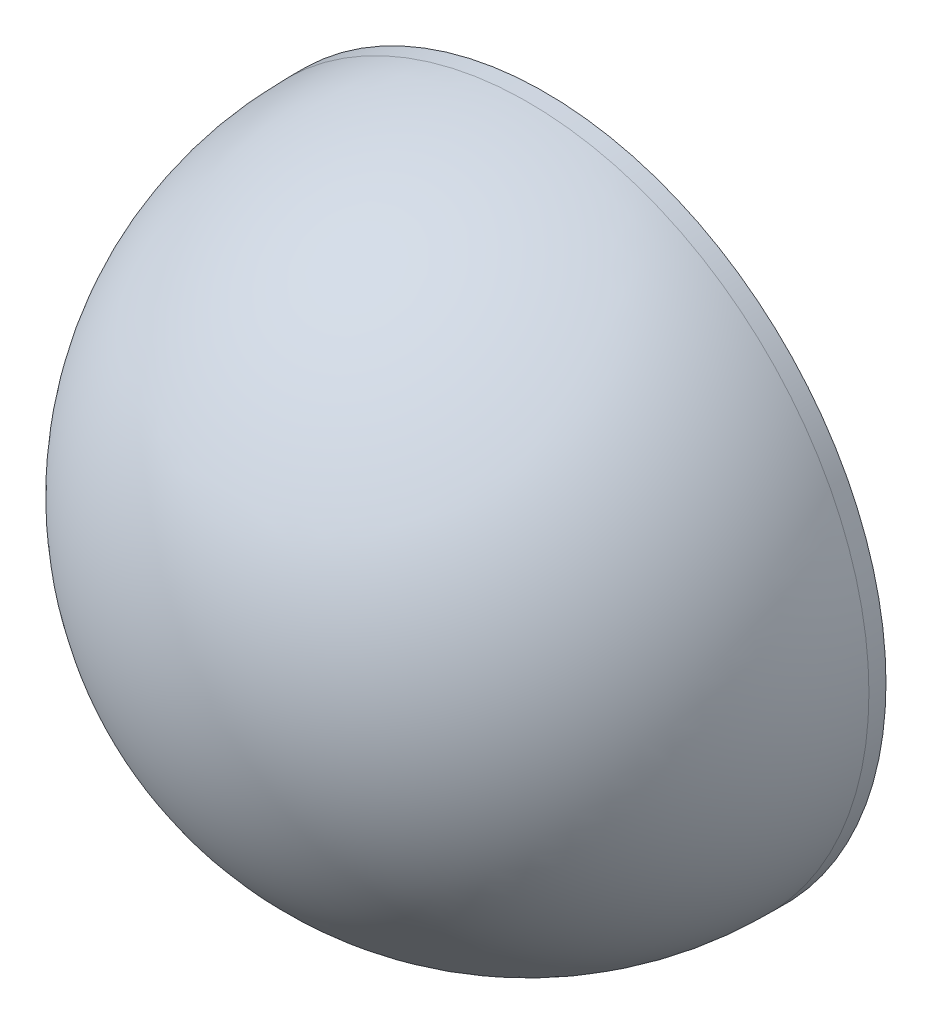
SolidWorks part; units mm, degrees
ref_plane "Front Plane" through (0, 0, 0) normal (0, 0, 1) x (1, 0, 0)
ref_plane "Top Plane" through (0, 0, 0) normal (0, 1, 0) x (1, 0, 0)
ref_plane "Right Plane" through (0, 0, 0) normal (1, 0, 0) x (0, 0, -1)
sketch "Sketch1" plane through (0, 0, 0) normal (0, 0, 1) x (1, 0, 0)
  circle A0 centre (-47.1485, 20.7453) radius 20
  dimension "D1" = 40
extrude "Boss-Extrude1" add sketch "Sketch1" along normal blind 1
dome "Dome1" faces to dome 1 distance 20 reverse direction no elliptical dome no face at (-27.1485, 20.7453, 1) parameters "D1"=20
shell "Shell1" thickness 3 removed face at (-27.1485, 20.7453, 0)
sketch "Sketch2" plane through (0, 0, 0) normal (0, 0, -1) x (-1, 0, 0)
  circle A0 centre (47.1485, 20.7453) radius 5
  dimension "D1" = 10
extrude "Boss-Extrude2" add sketch "Sketch2" against normal blind 20
sketch "Sketch3" plane through (0, 0, 0) normal (0, 0, -1) x (-1, 0, 0)
  circle A0 centre (47.1485, 20.7453) radius 18.75
  dimension "D1" = 37.5
extrude "Boss-Extrude3" add sketch "Sketch3" against normal blind 1
